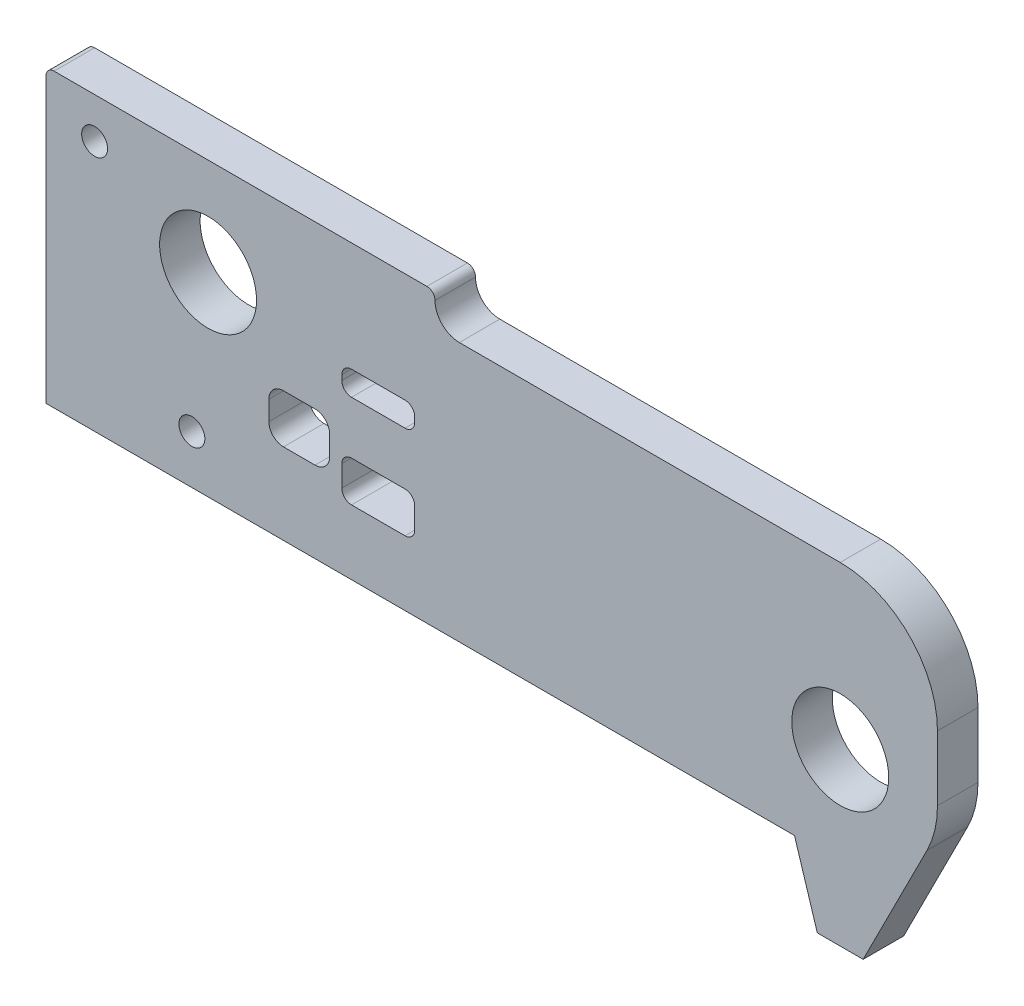
SolidWorks part; units mm, degrees
material "6061-T6 Black anodised"
ref_plane "Front Plane" through (0, 0, 0) normal (0, 0, 1) x (1, 0, 0)
ref_plane "Top Plane" through (0, 0, 0) normal (0, 1, 0) x (1, 0, 0)
ref_plane "Right Plane" through (0, 0, 0) normal (1, 0, 0) x (0, 0, -1)
sketch "Sketch1" plane through (0, 0, 0) normal (0, 0, 1) x (1, 0, 0)
  line L0 (72.3566, -24) -> (75.1721, -33)
  line L1 (-20, 12) -> (28, 12)
  line L2 (-20, 12) -> (-20, -24)
  line L3 (-20, -24) -> (72.3566, -24)
  line L4 (90, -4) -> (90, -12)
  line L5 (75.1721, -33) -> (80.8279, -33)
  line L6 (88.7087, -17.4151) -> (80.8279, -33)
  line L7 (25.5, -4.5) -> (25.5, -11) construction
  line L8 (16.5, -11) -> (25.5, -11)
  line L9 (16.5, -11) -> (16.5, -16)
  line L10 (16.5, -16) -> (25.5, -16)
  line L11 (25.5, -11) -> (25.5, -16)
  line L12 (16.5, -1.5) -> (25.5, -1.5)
  line L13 (16.5, -1.5) -> (16.5, -4.5)
  line L14 (16.5, -4.5) -> (25.5, -4.5)
  line L15 (25.5, -1.5) -> (25.5, -4.5)
  line L16 (28, 12) -> (28, 8)
  line L17 (7.5, -8) -> (15, -8)
  line L18 (7.5, -8) -> (7.5, -14)
  line L19 (7.5, -14) -> (15, -14)
  line L20 (15, -8) -> (15, -14)
  line L21 (28, 8) -> (78, 8)
  circle A0 centre (0, 0) radius 5.98
  circle A1 centre (78, -12) radius 5.98
  arc A3 (88.7087, -17.4151) -> (90, -12) centre (78, -12) ccw
  circle A4 centre (-14, 7) radius 1.6
  circle A5 centre (-2, -18) radius 1.6
  arc A6 (90, -4) -> (78, 8) centre (78, -4) ccw
  point P4 (-20, -6)
  point P13 (78, -33)
  point P29 (25.5, -10)
  dimension "D3" = 11.96
  dimension "D4" = 98
  dimension "D8" = 3.2
  dimension "D10" = 13
  dimension "D11" = 10
  dimension "D12" = 12
  dimension "D23" = 12
  dimension "D1" = 9
  dimension "D5" = 20
  dimension "D6" = 36
  dimension "D7" = 4
  dimension "D9" = 14
  dimension "D13" = 5.5
  dimension "D14" = 5
  dimension "D15" = 3
  dimension "D16" = 9
  dimension "D17" = 16.5
  dimension "D18" = 11
  dimension "D19" = 9
  dimension "D20" = 7.5
  dimension "D21" = 8
  dimension "D22" = 6
  dimension "D24" = 48
  dimension "D25" = 12
  dimension "D26" = 24
  dimension "D27" = 2
extrude "Boss-Extrude1" add sketch "Sketch1" along normal blind 5
fillet "Fillet1" radius 1.2 8 edges at (16.5, -4.5, 2.5) (16.5, -1.5, 2.5) (25.5, -1.5, 2.5) (25.5, -4.5, 2.5) (25.5, -16, 2.5) (25.5, -11, 2.5) (16.5, -11, 2.5) (16.5, -16, 2.5)
fillet "Fillet2" radius 3 1 edges at (28, 8, 2.5)
fillet "Fillet3" radius 1 2 edges at (28, 12, 2.5) (-20, 12, 2.5)
sketch "Sketch2" plane through (0, 0, 5) normal (0, 0, 1) x (1, 0, 0)
  line L0 (35, -13) -> (68, -19) construction
  line L1 (35, -13) -> (68, -13)
  line L2 (35, -13) -> (35, -15.25)
  line L3 (35, -19) -> (68, -19)
  line L4 (68, -13) -> (68, -15.25)
  line L5 (36.5, -15.25) -> (35, -15.25)
  line L6 (36.5, -15.25) -> (36.5, -16.75)
  line L7 (36.5, -16.75) -> (35, -16.75)
  line L8 (68, -16.75) -> (68, -19)
  line L9 (36.5, -15.25) -> (35, -16.75) construction
  line L10 (36.5, -16.75) -> (35, -15.25) construction
  line L11 (66.5, -15.25) -> (68, -15.25)
  line L12 (66.5, -15.25) -> (66.5, -16.75)
  line L13 (66.5, -16.75) -> (68, -16.75)
  line L14 (-20, -24) -> (72.3566, -24) construction
  line L15 (66.5, -15.25) -> (68, -16.75) construction
  line L16 (66.5, -16.75) -> (68, -15.25) construction
  line L17 (68, -13) -> (35, -19) construction
  line L18 (35, -16.75) -> (35, -19)
  point P4 (35.75, -16)
  point P9 (67.25, -16)
  point P14 (51.5, -16)
  dimension "D1" = 1.5
  dimension "D2" = 33
  dimension "D3" = 6
  dimension "D4" = 1.5
  dimension "D5" = 68
  dimension "D6" = 5
extrude "Cut-Extrude1" [suppressed] cut sketch "Sketch2" against normal through all
fillet "Fillet4" [suppressed] radius 0.5
fillet "Fillet5" radius 1.8 4 edges at (15, -14, 2.5) (15, -8, 2.5) (7.5, -8, 2.5) (7.5, -14, 2.5)
equation "\"y-cross-rib-thickness\"=6"
equation "\"y-rib-thickness\"=6"
equation "\"bed-plate-thickness\"=6"
equation "\"x-plate-thickness\"=5"
equation "\"rod-diameter\"=12"
equation "\"t-nut-hole-diameter\"=3"
equation "\"y-plate-thickness\"=5"
equation "\"D1@Boss-Extrude1\"=\"y-plate-thickness\""
